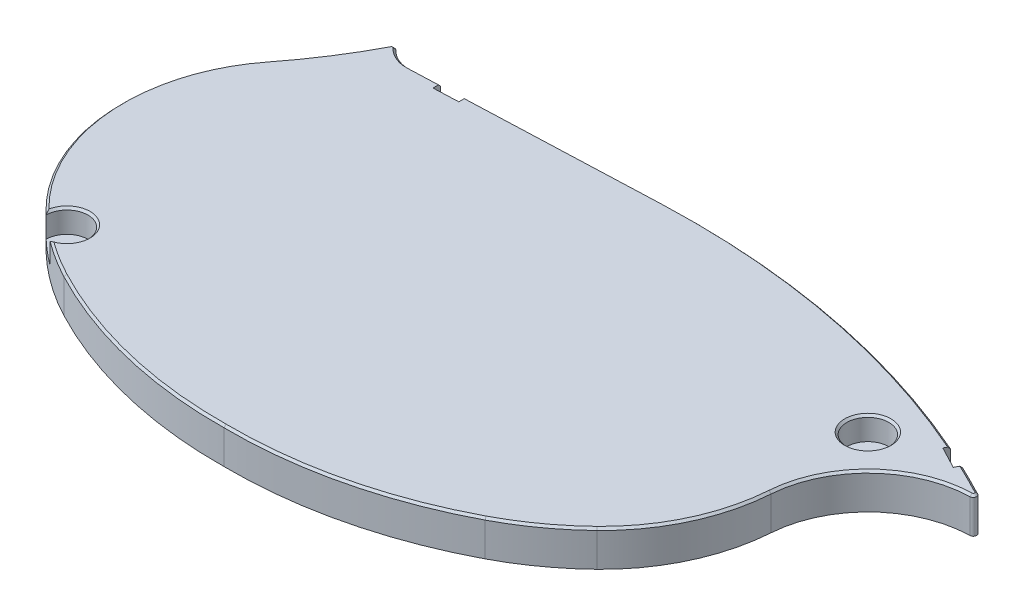
SolidWorks part; units mm, degrees
ref_plane "Front Plane" through (0, 0, 0) normal (0, 0, 1) x (1, 0, 0)
ref_plane "Top Plane" through (0, 0, 0) normal (0, 1, 0) x (1, 0, 0)
ref_plane "Right Plane" through (0, 0, 0) normal (1, 0, 0) x (0, 0, -1)
sketch "Main_line" plane through (0, 0, 0) normal (0, 1, 0) x (1, 0, 0)
  line L20 (-28.6085, 77.9005) -> (-86.778, 75.6599)
  line L21 (-28.6085, 77.9005) -> (-86.778, 75.6599) construction
  arc A175 (67.5413, 56.1577) -> (-28.6085, 77.9005) centre (-21.2537, -113.0414) ccw
  arc A176 (67.5413, 56.1577) -> (68.2565, 55.8322) centre (70.7942, 62.356) ccw
  arc A177 (67.9178, 53.9005) -> (68.2565, 55.8322) centre (67.894, 54.9002) ccw
  arc A178 (67.9178, 53.9005) -> (43.8878, 30.9723) centre (68.5072, 29.2264) ccw
  arc A179 (30.6398, 2.609) -> (43.8878, 30.9723) centre (0.2806, 34.0648) ccw
  arc A180 (15.1534, -8.5751) -> (30.6398, 2.609) centre (-16.1636, 51.103) ccw
  arc A181 (-35.0442, -20.6418) -> (15.1534, -8.5751) centre (-33.8372, 84.782) ccw
  arc A182 (-85.2418, -8.5751) -> (-35.0442, -20.6418) centre (-36.2512, 84.782) ccw
  arc A183 (-100.7282, 2.609) -> (-85.2418, -8.5751) centre (-53.9248, 51.103) ccw
  arc A184 (-113.2848, 42.3945) -> (-100.7282, 2.609) centre (-70.369, 34.0648) ccw
  arc A185 (-105.2065, 60.1333) -> (-113.2848, 42.3945) centre (-72.3034, 34.4402) ccw
  arc A186 (-105.2065, 60.1333) -> (-93.8493, 77.7344) centre (-197.1184, 131.9044) ccw
  arc A187 (-92.2242, 77.943) -> (-93.8493, 77.7344) centre (-92.9638, 77.2698) ccw
  arc A188 (-92.2242, 77.943) -> (-86.778, 75.6599) centre (-87.0474, 82.6547) ccw
  arc A189 (67.5413, 56.1577) -> (-28.6085, 77.9005) centre (-21.2537, -113.0414) ccw construction
  arc A190 (67.5413, 56.1577) -> (68.2565, 55.8322) centre (70.7942, 62.356) ccw construction
  arc A191 (67.9178, 53.9005) -> (68.2565, 55.8322) centre (67.894, 54.9002) ccw construction
  arc A192 (67.9178, 53.9005) -> (43.8878, 30.9723) centre (68.5072, 29.2264) ccw construction
  arc A193 (30.6398, 2.609) -> (43.8878, 30.9723) centre (0.2806, 34.0648) ccw construction
  arc A194 (15.1534, -8.5751) -> (30.6398, 2.609) centre (-16.1636, 51.103) ccw construction
  arc A195 (-35.0442, -20.6418) -> (15.1534, -8.5751) centre (-33.8372, 84.782) ccw construction
  arc A196 (-85.2418, -8.5751) -> (-35.0442, -20.6418) centre (-36.2512, 84.782) ccw construction
  arc A197 (-100.7282, 2.609) -> (-85.2418, -8.5751) centre (-53.9248, 51.103) ccw construction
  arc A198 (-113.2848, 42.3945) -> (-100.7282, 2.609) centre (-70.369, 34.0648) ccw construction
  arc A199 (-105.2065, 60.1333) -> (-113.2848, 42.3945) centre (-72.3034, 34.4402) ccw construction
  arc A200 (-105.2065, 60.1333) -> (-93.8493, 77.7344) centre (-197.1184, 131.9044) ccw construction
  arc A201 (-92.2242, 77.943) -> (-93.8493, 77.7344) centre (-92.9638, 77.2698) ccw construction
  arc A202 (-92.2242, 77.943) -> (-86.778, 75.6599) centre (-87.0474, 82.6547) ccw construction
  circle A217 centre (42.9558, 54.7596) radius 1.35 construction
  circle A218 centre (42.9558, 54.7596) radius 1.35 construction
  circle A219 centre (-95.0568, 2.2066) radius 1.35 construction
  dimension "D1" = 0
sketch "Sketch1" plane through (0, 0, 0) normal (0, 1, 0) x (1, 0, 0)
  line L0 (-79.7335, 75.7311) -> (-79.6643, 73.9324) construction
  line L1 (-79.6643, 73.9324) -> (-79.7412, 75.9309) construction
  line L2 (-79.6643, 73.9324) -> (-73.7526, 74.1601) construction
  line L3 (-73.8295, 76.1587) -> (-73.7526, 74.1601) construction
  line L4 (-73.7526, 74.1601) -> (-73.8218, 75.9588) construction
  line L5 (-73.7526, 74.1601) -> (-79.6643, 73.9324) construction
  line L6 (55.7698, 61.6122) -> (55.138, 60.4083) construction
  line L7 (55.138, 60.4083) -> (60.3765, 57.6591) construction
  line L8 (60.3765, 57.6591) -> (61.1526, 59.1379) construction
  line L9 (61.2456, 59.3151) -> (60.3765, 57.6591) construction
  line L10 (55.138, 60.4083) -> (55.863, 61.7897) construction
  line L16 (-28.6008, 77.7006) -> (-86.7703, 75.46)
  line L18 (-28.6008, 77.7006) -> (-86.7703, 75.46)
  circle A105 centre (42.9558, 54.7596) radius 1.35
  circle A107 centre (-95.0568, 2.2066) radius 1.35
  circle A108 centre (42.9558, 54.7596) radius 1.35 construction
  arc A119 (-92.3721, 77.8083) -> (-86.7703, 75.46) centre (-87.0474, 82.6547) ccw
  arc A120 (-92.3721, 77.8083) -> (-93.6722, 77.6415) centre (-92.9638, 77.2698) ccw
  arc A121 (-105.0488, 60.0102) -> (-93.6722, 77.6415) centre (-197.1184, 131.9044) ccw
  arc A122 (-105.0488, 60.0102) -> (-113.0885, 42.3564) centre (-72.3034, 34.4402) ccw
  arc A123 (-113.0885, 42.3564) -> (-100.5893, 2.7529) centre (-70.369, 34.0648) ccw
  arc A124 (-100.5893, 2.7529) -> (-85.1488, -8.398) centre (-53.9248, 51.103) ccw
  arc A125 (-85.1488, -8.398) -> (-35.0442, -20.4417) centre (-36.2512, 84.782) ccw
  arc A126 (-35.0442, -20.4417) -> (15.0605, -8.398) centre (-33.8372, 84.782) ccw
  arc A127 (15.0605, -8.398) -> (30.5009, 2.7529) centre (-16.1636, 51.103) ccw
  arc A128 (30.5009, 2.7529) -> (43.6883, 30.9864) centre (0.2806, 34.0648) ccw
  arc A129 (67.9131, 54.1005) -> (43.6883, 30.9864) centre (68.5072, 29.2264) ccw
  arc A130 (67.9131, 54.1005) -> (68.184, 55.6458) centre (67.894, 54.9002) ccw
  arc A131 (67.4484, 55.9806) -> (68.184, 55.6458) centre (70.7942, 62.356) ccw
  arc A132 (67.4484, 55.9806) -> (-28.6008, 77.7006) centre (-21.2537, -113.0414) ccw
  arc A147 (-92.3721, 77.8083) -> (-86.7703, 75.46) centre (-87.0474, 82.6547) ccw
  arc A148 (-92.3721, 77.8083) -> (-93.6722, 77.6415) centre (-92.9638, 77.2698) ccw
  arc A149 (-105.0488, 60.0102) -> (-93.6722, 77.6415) centre (-197.1184, 131.9044) ccw
  arc A150 (-105.0488, 60.0102) -> (-113.0885, 42.3564) centre (-72.3034, 34.4402) ccw
  arc A151 (-113.0885, 42.3564) -> (-100.5893, 2.7529) centre (-70.369, 34.0648) ccw
  arc A152 (-100.5893, 2.7529) -> (-85.1488, -8.398) centre (-53.9248, 51.103) ccw
  arc A153 (-85.1488, -8.398) -> (-35.0442, -20.4417) centre (-36.2512, 84.782) ccw
  arc A154 (-35.0442, -20.4417) -> (15.0605, -8.398) centre (-33.8372, 84.782) ccw
  arc A155 (15.0605, -8.398) -> (30.5009, 2.7529) centre (-16.1636, 51.103) ccw
  arc A156 (30.5009, 2.7529) -> (43.6883, 30.9864) centre (0.2806, 34.0648) ccw
  arc A157 (67.9131, 54.1005) -> (43.6883, 30.9864) centre (68.5072, 29.2264) ccw
  arc A158 (67.9131, 54.1005) -> (68.184, 55.6458) centre (67.894, 54.9002) ccw
  arc A159 (67.4484, 55.9806) -> (68.184, 55.6458) centre (70.7942, 62.356) ccw
  arc A160 (67.4484, 55.9806) -> (-28.6008, 77.7006) centre (-21.2537, -113.0414) ccw
  point P10 (55.7698, 61.6122)
  dimension "D1" = 0.2
extrude "Boss-Extrude1" add sketch "Sketch1" along normal blind 3
sketch "Sketch3" plane through (0, 0, 0) normal (0, -1, 0) x (1, 0, 0)
  circle A0 centre (42.9558, -54.7596) radius 2.5
  circle A1 centre (-95.0568, -2.2066) radius 2.5
  dimension "D1" = 5
extrude "Cut-Extrude1" cut sketch "Sketch3" against normal blind 1.7
chamfer "Chamfer1" distance 1.2 angle 45 2 edges at (42.9558, 1.7, -57.2596) (-95.0568, 1.7, -4.7066)
sketch "Sketch4" plane through (0, 3, 0) normal (0, 1, 0) x (1, 0, 0)
  line L16 (-28.6008, 77.7006) -> (-86.7703, 75.46)
  line L17 (-28.6008, 77.7006) -> (-86.7703, 75.46)
  arc A4 (-100.0567, 2.2444) -> (-94.1635, -2.713) centre (-95.0568, 2.2066) cw
  circle A5 centre (42.9558, 54.7596) radius 5
  arc A6 (-94.1635, -2.713) -> (-85.1488, -8.398) centre (-53.9248, 51.103) ccw
  arc A123 (-92.3721, 77.8083) -> (-86.7703, 75.46) centre (-87.0474, 82.6547) ccw
  arc A124 (-92.3721, 77.8083) -> (-93.6722, 77.6415) centre (-92.9638, 77.2698) ccw
  arc A125 (-105.0488, 60.0102) -> (-93.6722, 77.6415) centre (-197.1184, 131.9044) ccw
  arc A126 (-105.0488, 60.0102) -> (-113.0885, 42.3564) centre (-72.3034, 34.4402) ccw
  arc A127 (-113.0885, 42.3564) -> (-100.5893, 2.7529) centre (-70.369, 34.0648) ccw
  arc A128 (-100.5893, 2.7529) -> (-85.1488, -8.398) centre (-53.9248, 51.103) ccw
  arc A129 (-85.1488, -8.398) -> (-35.0442, -20.4417) centre (-36.2512, 84.782) ccw
  arc A130 (-35.0442, -20.4417) -> (15.0605, -8.398) centre (-33.8372, 84.782) ccw
  arc A131 (15.0605, -8.398) -> (30.5009, 2.7529) centre (-16.1636, 51.103) ccw
  arc A132 (30.5009, 2.7529) -> (43.6883, 30.9864) centre (0.2806, 34.0648) ccw
  arc A133 (67.9131, 54.1005) -> (43.6883, 30.9864) centre (68.5072, 29.2264) ccw
  arc A134 (67.9131, 54.1005) -> (68.184, 55.6458) centre (67.894, 54.9002) ccw
  arc A135 (67.4484, 55.9806) -> (68.184, 55.6458) centre (70.7942, 62.356) ccw
  arc A136 (67.4484, 55.9806) -> (-28.6008, 77.7006) centre (-21.2537, -113.0414) ccw
  arc A137 (-92.3721, 77.8083) -> (-86.7703, 75.46) centre (-87.0474, 82.6547) ccw
  arc A138 (-92.3721, 77.8083) -> (-93.6722, 77.6415) centre (-92.9638, 77.2698) ccw
  arc A139 (-105.0488, 60.0102) -> (-93.6722, 77.6415) centre (-197.1184, 131.9044) ccw
  arc A140 (-105.0488, 60.0102) -> (-113.0885, 42.3564) centre (-72.3034, 34.4402) ccw
  arc A141 (-113.0885, 42.3564) -> (-100.5893, 2.7529) centre (-70.369, 34.0648) ccw
  arc A142 (-100.5893, 2.7529) -> (-100.0567, 2.2444) centre (-53.9248, 51.103) ccw
  arc A143 (-85.1488, -8.398) -> (-35.0442, -20.4417) centre (-36.2512, 84.782) ccw
  arc A144 (-35.0442, -20.4417) -> (15.0605, -8.398) centre (-33.8372, 84.782) ccw
  arc A145 (15.0605, -8.398) -> (30.5009, 2.7529) centre (-16.1636, 51.103) ccw
  arc A146 (30.5009, 2.7529) -> (43.6883, 30.9864) centre (0.2806, 34.0648) ccw
  arc A147 (67.9131, 54.1005) -> (43.6883, 30.9864) centre (68.5072, 29.2264) ccw
  arc A148 (67.9131, 54.1005) -> (68.184, 55.6458) centre (67.894, 54.9002) ccw
  arc A149 (67.4484, 55.9806) -> (68.184, 55.6458) centre (70.7942, 62.356) ccw
  arc A150 (67.4484, 55.9806) -> (-28.6008, 77.7006) centre (-21.2537, -113.0414) ccw
  dimension "D1" = 10
  dimension "D3" = 0
extrude "Boss-Extrude2" add sketch "Sketch4" along normal blind 5.5
chamfer "Chamfer2" distance 0.5 angle 45 2 edges at (-91.8382, 8.5, -6.0328) (42.9558, 8.5, -49.7596)
chamfer "Chamfer3" distance 0.5 angle 45 16 edges at (-89.4893, 8.5, 5.91) (-60.8451, 8.5, 17.5343) (-9.2432, 8.5, 17.5343) (23.1778, 8.5, 3.3724) (39.7085, 8.5, -15.6488) (51.331, 8.5, -47.2279) (68.6819, 8.5, -54.7621) (67.8115, 8.5, -55.8029) (20.8486, 8.5, -73.1411) (-57.6855, 8.5, -76.5803) (-89.831, 8.5, -76.0145) (-93.0656, 8.5, -78.0633) (-98.9638, 8.5, -68.5699) (-110.1134, 8.5, -51.6591) (-111.8679, 8.5, -20.9674) (-100.562, 8.5, -2.7265)
sketch "Sketch5" plane through (0, 8.5, 0) normal (0, 1, 0) x (1, 0, 0)
  line L0 (-79.7335, 75.7311) -> (-79.6643, 73.9324)
  line L1 (-79.6643, 73.9324) -> (-73.7526, 74.1601)
  line L2 (-73.7526, 74.1601) -> (-73.8218, 75.9588)
  line L3 (-73.8218, 75.9588) -> (-79.7335, 75.7311)
  line L4 (55.7698, 61.6122) -> (55.138, 60.4083)
  line L5 (55.138, 60.4083) -> (60.3765, 57.6591)
  line L6 (60.3765, 57.6591) -> (61.1526, 59.1379)
  line L7 (61.1526, 59.1379) -> (61.6173, 60.0234)
  line L8 (61.6173, 60.0234) -> (56.3787, 62.7725)
  line L9 (56.3787, 62.7725) -> (55.7698, 61.6122)
  dimension "D1" = 1
extrude "Cut-Extrude3" cut sketch "Sketch5" against normal blind 5
